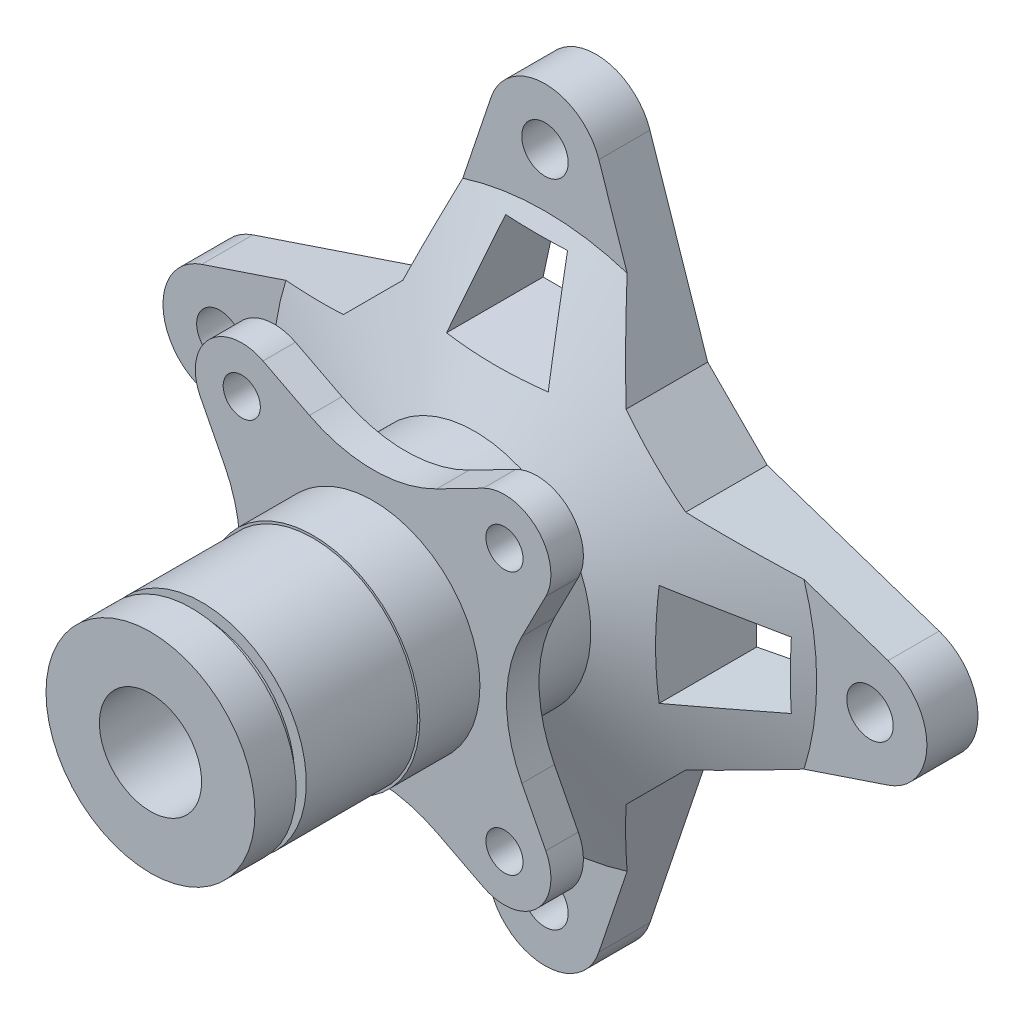
SolidWorks part; units mm, degrees
ref_plane "Front Plane" through (0, 0, 0) normal (0, 0, 1) x (1, 0, 0)
ref_plane "Top Plane" through (0, 0, 0) normal (0, 1, 0) x (1, 0, 0)
ref_plane "Right Plane" through (0, 0, 0) normal (1, 0, 0) x (0, 0, -1)
sketch "Sketch1" plane through (0, 0, 0) normal (0, 0, 1) x (1, 0, 0)
  line L0 (0, 104.8278) -> (0, 81.6378) construction
  line L1 (-36.8516, 58.8694) -> (-24.0416, 71.6794)
  line L2 (70, 34.8278) -> (46.81, 34.8278) construction
  line L3 (24.0416, 71.6794) -> (36.8516, 58.8694)
  line L4 (-36.8516, 10.7861) -> (-24.0416, -2.0239)
  line L5 (36.8516, 10.7861) -> (24.0416, -2.0239)
  line L6 (-46.81, 34.8278) -> (-70, 34.8278) construction
  line L7 (0, -11.9822) -> (0, -35.1722) construction
  line L8 (21.19, 34.8278) -> (-21.19, 34.8278) construction
  line L9 (0, 56.0178) -> (0, 13.6378) construction
  line L10 (11.6139, 108.724) -> (24.0416, 71.6794)
  line L11 (73.8962, 46.4416) -> (36.8516, 58.8694)
  line L12 (73.8962, 23.2139) -> (36.8516, 10.7861)
  line L13 (11.6139, -39.0685) -> (24.0416, -2.0239)
  line L14 (-11.6139, -39.0685) -> (-24.0416, -2.0239)
  line L15 (-73.8962, 23.2139) -> (-36.8516, 10.7861)
  line L16 (-73.8962, 46.4416) -> (-36.8516, 58.8694)
  line L17 (-11.6139, 108.724) -> (-24.0416, 71.6794)
  circle A0 centre (0, 34.8278) radius 18.5
  circle A1 centre (0, 104.8278) radius 5
  circle A2 centre (70, 34.8278) radius 5
  circle A3 centre (-70, 34.8278) radius 5
  circle A4 centre (0, -35.1722) radius 5
  circle A5 centre (0, 34.8278) radius 12.81
  arc A6 (-36.8516, 58.8694) -> (-36.8516, 10.7861) centre (-12.81, 34.8278) ccw
  arc A8 (36.8516, 10.7861) -> (36.8516, 58.8694) centre (12.81, 34.8278) ccw
  arc A9 (-24.0416, -2.0239) -> (24.0416, -2.0239) centre (0, 22.0178) ccw
  circle A10 centre (-70, 34.8278) radius 12.25
  arc A11 (24.0416, 71.6794) -> (-24.0416, 71.6794) centre (0, 47.6378) ccw
  circle A12 centre (0, 104.8278) radius 12.25
  circle A13 centre (70, 34.8278) radius 12.25
  circle A14 centre (0, -35.1722) radius 12.25
  dimension "D1" = 37
extrude "Boss-Extrude1" add sketch "Sketch1" along normal blind 11 contours A10 L15 A6 L16 | A10 A3 | L3 A11 L1 A6 L4 A9 L5 A8 A0 | A12 L17 A11 L10 | A12 A1 | A13 L11 A8 L12 | A13 A2 | A14 L13 A9 L14 | A14 A4 region at (-52.5929, 34.8278, 0) region at (-29.5104, 64.3382, 0) region at (0, 87.4207, 0) region at (-63.0492, 44.4911, 0) region at (0, 116.7313, 0) region at (0, -17.7651, 0) region at (52.5929, 34.8278, 0) region at (-1.9181, -23.4243, 0) region at (79.6634, 41.7786, 0)
sketch "Sketch3" plane through (0, 0, 11) normal (0, 0, 1) x (1, 0, 0)
  point P0 (0, 34.8278)
  point P1 (0, 0)
ref_plane "Plane1" through (17.4139, 17.4139, 0) normal (-0.7071, -0.7071, 0) x (-0.7071, 0.7071, 0)
sketch "Sketch4" plane through (17.4139, 17.4139, 0) normal (-0.7071, -0.7071, 0) x (-0.7071, 0.7071, 0)
  line L0 (24.627, -11) -> (-0.373, -11)
  line L1 (-0.373, -11) -> (-0.373, -26.1163)
  line L2 (-0.373, -26.1163) -> (-33.8894, -11)
  line L3 (-33.8894, -11) -> (-0.373, -11)
  line L4 (24.627, -11) -> (24.627, -221.32) construction
  dimension "D1" = 25
revolve "Revolve1" add sketch "Sketch4" angle 360 about L4 region at (25.5775, 9.2502, 16.0388)
sketch "Sketch5" plane through (0, 0, 0) normal (0, 0, -1) x (-1, 0, 0)
  line L0 (0.3929, 34.8278) -> (55.393, 34.8278) construction
  line L1 (0.3929, 34.8278) -> (-50.523, 34.8278) construction
  line L2 (0.3929, 34.8278) -> (0.3929, 104.8278) construction
  line L3 (0.3929, 34.8278) -> (0.3929, -35.1722) construction
  line L4 (-10.6071, 69.8278) -> (11.3929, 69.8278)
  line L5 (-6.2929, 89.8278) -> (7.0788, 89.8278)
  line L6 (-10.6071, 69.8278) -> (-6.2929, 89.8278)
  line L7 (11.3929, 69.8278) -> (7.0788, 89.8278)
  line L8 (-10.6071, -0.1722) -> (11.3929, -0.1722)
  line L9 (-10.6071, -0.1722) -> (-6.2929, -20.1722)
  line L10 (-6.2929, -20.1722) -> (7.0788, -20.1722)
  line L11 (11.3929, -0.1722) -> (7.0788, -20.1722)
  line L12 (-34.6071, 23.8278) -> (-34.6071, 45.8278)
  line L13 (-54.6071, 27.7071) -> (-54.6071, 41.9485)
  line L14 (-34.6071, 23.8278) -> (-54.6071, 27.7071)
  line L15 (-34.6071, 45.8278) -> (-54.6071, 41.9485)
  line L16 (35.3929, 23.8278) -> (35.3929, 45.8278)
  line L17 (35.3929, 23.8278) -> (55.3929, 27.7071)
  line L18 (55.3929, 27.7071) -> (55.3929, 41.9485)
  line L19 (35.3929, 45.8278) -> (55.3929, 41.9485)
  line L20 (-55.7776, 52.5201) -> (-36.8516, 58.8694)
  line L21 (-73.8962, 46.4416) -> (-36.8516, 58.8694) construction
  line L22 (-36.8516, 58.8694) -> (-24.0416, 71.6794)
  line L23 (-24.0416, 71.6794) -> (-17.6923, 90.6054)
  line L24 (17.6923, 90.6054) -> (24.0416, 71.6794)
  line L25 (24.0416, 71.6794) -> (36.8516, 58.8694)
  line L26 (36.8516, 58.8694) -> (55.3739, 52.6555)
  line L27 (73.8962, 46.4416) -> (36.8516, 58.8694) construction
  line L28 (55.7776, 17.1355) -> (36.8516, 10.7861)
  line L29 (36.8516, 10.7861) -> (24.0416, -2.0239)
  line L30 (17.6923, -20.9498) -> (24.0416, -2.0239)
  line L31 (-17.6923, -20.9498) -> (-24.0416, -2.0239)
  line L32 (-24.0416, -2.0239) -> (-36.8516, 10.7861)
  line L33 (-36.8516, 10.7861) -> (-55.3739, 17)
  line L34 (-73.8962, 23.2139) -> (-36.8516, 10.7861) construction
  circle A3 centre (0, 34.8278) radius 58.5163
  point P6 (0.3929, 69.8278)
  point P11 (0.3929, 89.8278)
  point P18 (-34.6071, 34.8278)
  point P21 (40.3929, 34.8532)
  point P22 (-54.6071, 34.8278)
  point P24 (55.393, 34.8278)
  line M20 (73.8962, 46.4416) -> (36.8516, 58.8694)
  line M21 (36.8516, 58.8694) -> (24.0416, 71.6794)
  line M22 (24.0416, 71.6794) -> (11.6139, 108.724)
  line M24 (-11.6139, 108.724) -> (-24.0416, 71.6794)
  line M25 (-24.0416, 71.6794) -> (-36.8516, 58.8694)
  line M26 (-36.8516, 58.8694) -> (-73.8962, 46.4416)
  line M28 (-73.8962, 23.2139) -> (-36.8516, 10.7861)
  line M29 (-36.8516, 10.7861) -> (-24.0416, -2.0239)
  line M30 (-24.0416, -2.0239) -> (-11.6139, -39.0685)
  line M32 (11.6139, -39.0685) -> (24.0416, -2.0239)
  line M33 (24.0416, -2.0239) -> (36.8516, 10.7861)
  line M34 (36.8516, 10.7861) -> (73.8962, 23.2139)
  dimension "D1" = 35
  dimension "D2" = 22
  dimension "D3" = 20
  dimension "D4" = 35
  dimension "D5" = 22
  dimension "D6" = 20
extrude "Cut-Extrude1" cut sketch "Sketch5" against normal through all contours A3 M24 M26 M25 | A3 M20 M22 M21 | A3 M32 M34 M33 | L19 L16 L17 L18 | L4 L7 L5 L6 | L12 L15 L13 L14 | L11 L8 L9 L10 | A3 M28 M30 M29 region at (-0.3929, 79.0147, 0) region at (-0.3929, -9.3591, 0) region at (43.8935, 34.8278, 0) region at (-44.6793, 34.8278, 0) region at (36.0285, 70.8563, 0) region at (36.0285, -1.2008, 0) region at (-36.0285, 70.8563, 0) region at (-36.0285, -1.2008, 0)
sketch "Sketch6" plane through (0, 0, 11) normal (0, 0, 1) x (1, 0, 0)
  circle A0 centre (0, 34.8278) radius 25
  circle A1 centre (0, 34.8278) radius 18.5
extrude "Boss-Extrude2" add sketch "Sketch6" along normal blind 37
sketch "Sketch7" plane through (0, 0, 48) normal (0, 0, 1) x (1, 0, 0)
  line L0 (0, 34.8278) -> (58.0469, 92.8747) construction
  line L1 (58.0469, 92.8747) -> (-58.2346, -23.4068) construction
  line L2 (-58.2346, -23.4068) -> (0, 34.8278) construction
  line L3 (0, 34.8278) -> (51.9152, -17.0874) construction
  line L4 (10.4245, 24.4033) -> (24.4033, 10.4245) construction
  line L5 (51.9152, -17.0874) -> (-64.2463, 99.074) construction
  line L6 (-37.1797, 11.112) -> (-25, 34.8278)
  line L7 (-23.7158, -2.352) -> (0, 9.8278)
  line L8 (0, 34.8278) -> (0, -9.0872) construction
  line L9 (37.1797, 11.112) -> (25, 34.8278)
  line L10 (23.7158, -2.352) -> (0, 9.8278)
  line L11 (0, 34.8278) -> (41.9672, 34.8278) construction
  line L12 (37.1797, 58.5436) -> (25, 34.8278)
  line L13 (23.7158, 72.0075) -> (0, 59.8278)
  line L14 (-23.7158, 72.0075) -> (0, 59.8278)
  line L15 (-37.1797, 58.5436) -> (-25, 34.8278)
  circle A0 centre (0, 34.8278) radius 25
  circle A3 centre (-28.2843, 6.5435) radius 4
  circle A4 centre (-28.2843, 6.5435) radius 10
  circle A5 centre (28.2843, 6.5435) radius 4
  circle A6 centre (28.2843, 6.5435) radius 10
  circle A7 centre (28.2843, 63.112) radius 4
  circle A8 centre (28.2843, 63.112) radius 10
  circle A9 centre (-28.2843, 63.112) radius 4
  circle A10 centre (-28.2843, 63.112) radius 10
  circle M13 centre (0, 34.8278) radius 25
  dimension "D1" = 40
extrude "Boss-Extrude3" add sketch "Sketch7" against normal blind 7 contours A10 A9 | L14 A10 L15 M13 | A4 L7 L6 M13 | A4 A3 | L10 A6 L9 M13 | A6 A5 | A8 L13 L12 M13 | A8 A7 region at (-19.8915, 14.9363, 48) region at (-26.0007, 15.9885, 48) region at (-19.8915, 54.7193, 48) region at (-35.1553, 69.9831, 48) region at (19.8915, 54.7193, 48) region at (19.8915, 14.9363, 48) region at (33.3482, 71.4054, 48) region at (21.4132, 13.4146, 48)
sketch "Sketch8" plane through (0, 0, 48) normal (0, 0, 1) x (1, 0, 0)
  circle A0 centre (0, 34.8278) radius 18.5
  circle A1 centre (0, 34.8278) radius 23
extrude "Boss-Extrude4" add sketch "Sketch8" along normal blind 12.94
sketch "Sketch9" plane through (0, 0, 60.94) normal (0, 0, 1) x (1, 0, 0)
  circle A0 centre (0, 34.8278) radius 11
  circle A1 centre (0, 34.8278) radius 22.5
  dimension "D1" = 45
extrude "Boss-Extrude5" add sketch "Sketch9" along normal blind 44 from offset 9 offset against normal yes
fillet "Fillet1" radius 30 1 edges at (25, 34.8278, 44.5) type face fillet first side face at (31.0899, 22.9699, 44.5) second side face at (31.0899, 46.6857, 44.5)
fillet "Fillet2" radius 30 1 edges at (0, 9.8278, 44.5) type face fillet first side face at (-11.8579, 3.7379, 44.5) second side face at (11.8579, 3.7379, 44.5)
fillet "Fillet3" radius 30 1 edges at (-25, 34.8278, 44.5) type face fillet first side face at (-31.0899, 22.9699, 44.5) second side face at (-31.0899, 46.6857, 44.5)
fillet "Fillet4" radius 30 1 edges at (0, 59.8278, 44.5) type face fillet first side face at (-11.8579, 65.9176, 44.5) second side face at (11.8579, 65.9176, 44.5)
ref_plane "Plane2" through (0, 0, 87.08) normal (0, 0, -1) x (-1, 0, 0)
sketch "Sketch11" plane through (0, 0, 87.08) normal (0, 0, -1) x (-1, 0, 0)
  circle A0 centre (0, 34.8278) radius 20
  circle A1 centre (0, 34.8278) radius 22.5
extrude "Cut-Extrude2" cut sketch "Sketch11" along normal blind 2.2
